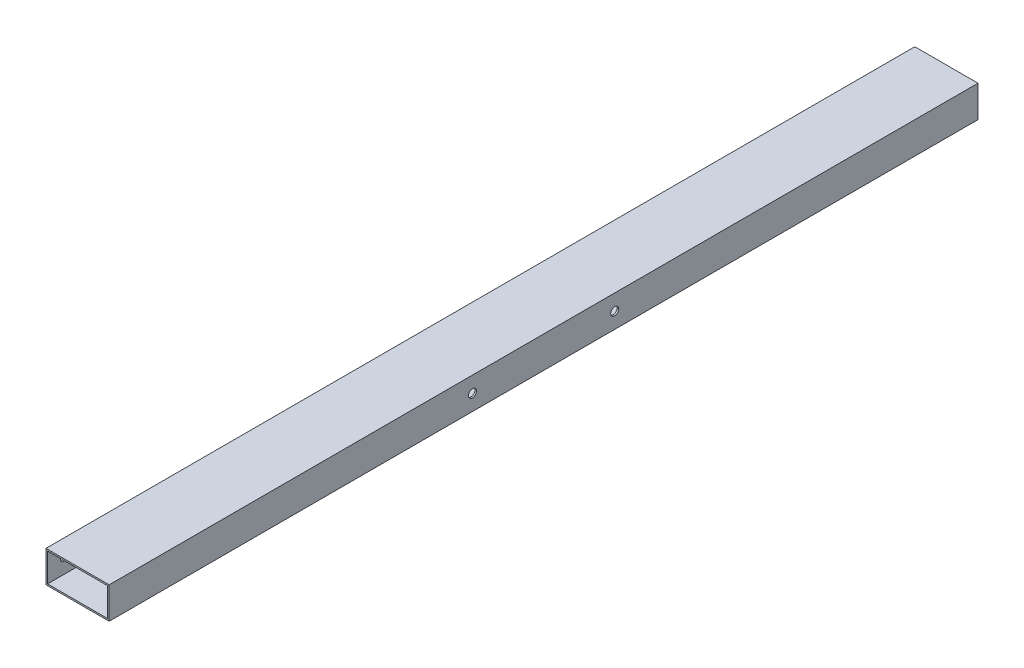
SolidWorks part; units mm, degrees
material "1060 合金"
ref_plane "前视基准面" through (0, 0, 0) normal (0, 0, 1) x (1, 0, 0)
ref_plane "上视基准面" through (0, 0, 0) normal (0, 1, 0) x (1, 0, 0)
ref_plane "右视基准面" through (0, 0, 0) normal (1, 0, 0) x (0, 0, -1)
other "Configuration Table"
sketch "草图1" plane through (0, 0, 0) normal (0, 0, 1) x (1, 0, 0)
  line L1 (0, 0) -> (40, 0)
  line L2 (0, 0) -> (0, -20)
  line L3 (0, -20) -> (40, -20)
  line L4 (40, 0) -> (40, -20)
  dimension "D1" = 20
  dimension "D2" = 40
extrude "拉伸-薄壁1" add sketch "草图1" along normal blind 550 thin thin type one direction reverse wall 1
sketch "草图4" plane through (0, 0, 0) normal (-1, 0, 0) x (0, 0, 1)
  line L0 (550, 0) -> (0, 0) construction
  line L1 (550, 0) -> (550, -20) construction
  line L4 (0, -208.7901) -> (0, 661.2099) construction
  circle A1 centre (539.9964, -10) radius 1.75
  circle A49 centre (10, -10) radius 1.75
  dimension "D27" = 3.5
  dimension "D28" = 3.5
  dimension "D29" = 10
  dimension "D25" = 10
  dimension "D26" = 10.0036
  dimension "D30" = 10
extrude "切除-拉伸2" cut sketch "草图4" against normal blind 1.5
sketch "草图5" plane through (0, 0, 0) normal (-1, 0, 0) x (0, 0, 1)
  line L1 (550, 0) -> (0, 0) construction
  line L2 (0, -742.5) -> (0, 127.5) construction
  circle A25 centre (255, -10) radius 2.6
  dimension "D3" = 5.2
  dimension "D1" = 10
  dimension "D2" = 255
extrude "切除-拉伸3" cut sketch "草图5" against normal blind 1.5
sketch "草图6" plane through (40, 0, 0) normal (1, 0, 0) x (0, 0, -1)
  line L0 (-550, -20) -> (0, -20) construction
  line L1 (-550, -20) -> (-550, 0) construction
  line L2 (0, -20) -> (0, 0) construction
  circle A0 centre (-320, -10) radius 2.5
  circle A1 centre (-230, -10) radius 2.5
  dimension "D1" = 5
  dimension "D4" = 5
  dimension "D2" = 10
  dimension "D3" = 230
  dimension "D5" = 10
  dimension "D6" = 230
extrude "切除-拉伸4" cut sketch "草图6" against normal through all
